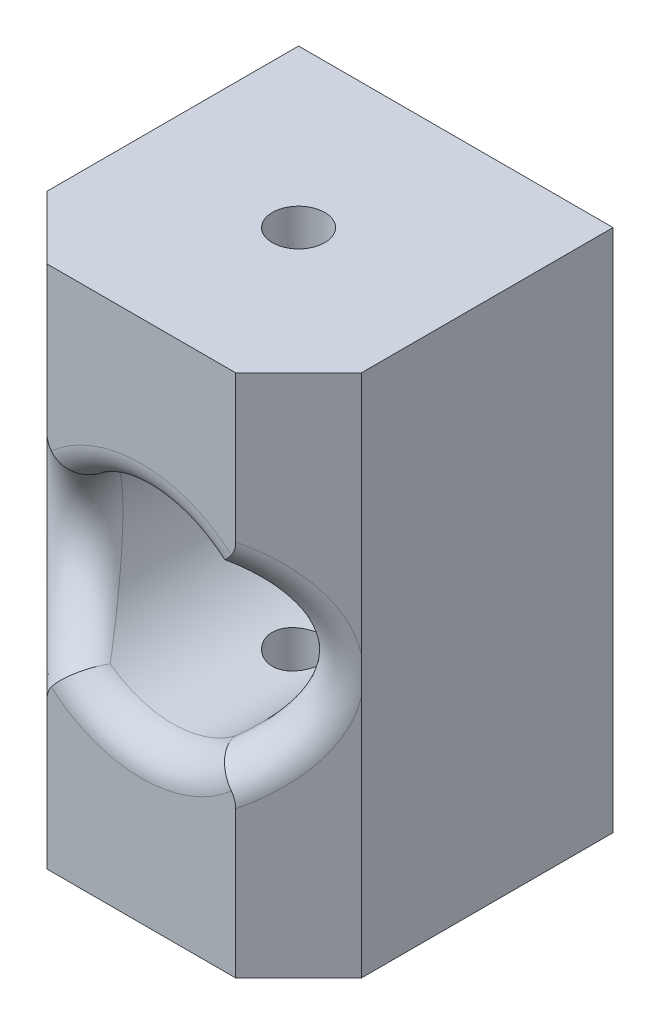
SolidWorks part; units mm, degrees
ref_plane "Ön Düzlem" through (0, 0, 0) normal (0, 0, 1) x (1, 0, 0)
ref_plane "Üst Düzlem" through (0, 0, 0) normal (0, 1, 0) x (1, 0, 0)
ref_plane "Sağ Düzlem" through (0, 0, 0) normal (1, 0, 0) x (0, 0, -1)
sketch "Çizim1" plane through (0, 0, 0) normal (0, 0, 1) x (1, 0, 0)
  line L1 (-15, 25) -> (15, 25)
  line L2 (-15, 25) -> (-15, -25)
  line L3 (-15, -25) -> (15, -25)
  line L4 (15, 25) -> (15, -25)
  dimension "D1" = 50
  dimension "D2" = 30
  dimension "D3" = 25
  dimension "D4" = 15
extrude "Yükseklik-Ekstrüzyon1" add sketch "Çizim1" along normal blind 30
chamfer "Pah1" distance 6 angle 45 2 edges at (15, 0, 30) (-15, 0, 30)
sketch "Çizim2" plane through (0, 0, 30) normal (0, 0, 1) x (1, 0, 0)
  circle A0 centre (0, 0) radius 10
  dimension "D1" = 20
extrude "Kes-Ekstrüzyon1" cut sketch "Çizim2" against normal up to surface (30 mm away) up to face at (0, 0, 0)
fillet "Radyus1" radius 3 4 edges at (10, 0, 29) (0, -10, 30) (-10, 0, 29) (0, 10, 30)
sketch "Çizim3" plane through (0, 25, 0) normal (0, 1, 0) x (1, 0, 0)
  line L0 (15, 0) -> (-15, 0) construction
  line L1 (-15, -24) -> (-15, 0) construction
  circle A0 centre (0, -15) radius 2.5
  dimension "D1" = 15
  dimension "D2" = 15
  dimension "D3" = 5
extrude "Kes-Ekstrüzyon2" cut sketch "Çizim3" against normal up to surface (50 mm away) up to face at (0, -25, 18)
